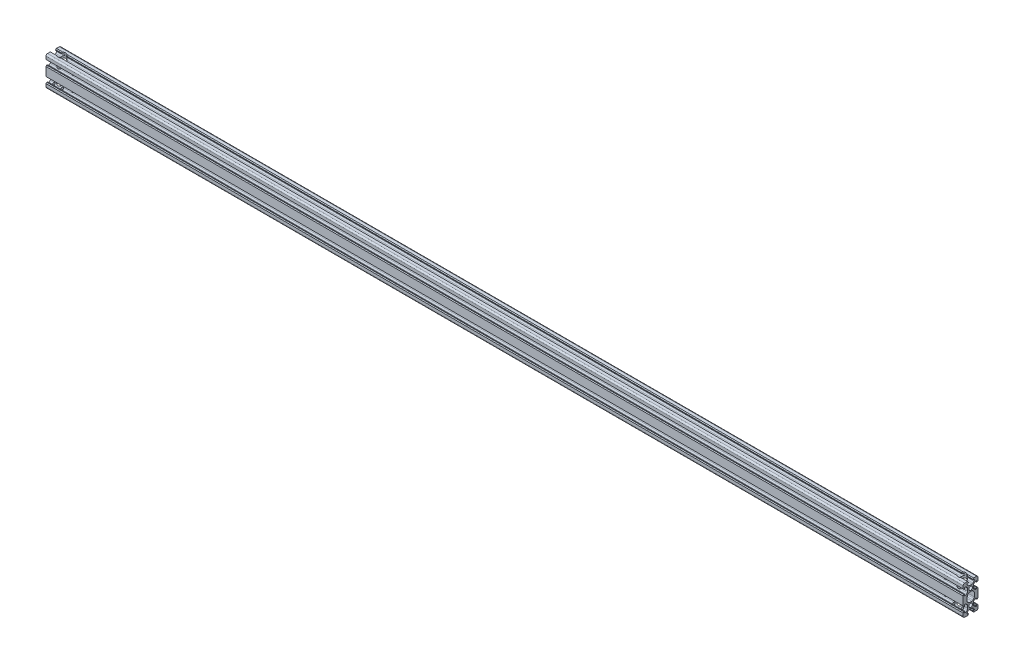
SolidWorks part; units mm, degrees
ref_plane "Front Plane" through (0, 0, 0) normal (0, 0, 1) x (1, 0, 0)
ref_plane "Top Plane" through (0, 0, 0) normal (0, 1, 0) x (1, 0, 0)
ref_plane "Right Plane" through (0, 0, 0) normal (1, 0, 0) x (0, 0, -1)
sketch "Sketch1" plane through (0, 0, 0) normal (1, 0, 0) x (0, 0, -1)
  line B0 (6.9, 38) -> (5, 38)
  line B1 (19, 6.9) -> (20, 5.9)
  line B2 (14.4142, 15.8284) -> (13.1236, 14.5379)
  line B3 (20, 14.1) -> (19, 13.1)
  line B4 (15.8284, 5.5858) -> (14.5379, 6.8764)
  line B5 (17.2426, 5) -> (18, 5)
  line B6 (18, 6.9) -> (18, 5)
  line B7 (17.2426, 15) -> (18, 15)
  line B8 (8.2906, 13.9521) -> (11.7094, 13.9521)
  line B9 (18, 15) -> (18, 13.1)
  line B10 (18, 13.1) -> (19, 13.1)
  line B11 (18, 6.9) -> (19, 6.9)
  line B12 (13.9521, 11.7094) -> (13.9521, 8.2906)
  line B13 (6.8764, 14.5379) -> (5.5858, 15.8284)
  line B14 (20, 5.9) -> (20, 2)
  line B15 (14.5379, 13.1236) -> (15.8284, 14.4142)
  line B16 (6.9, 1) -> (5.9, 0)
  line B17 (18, 0) -> (14.1, 0)
  line B18 (14.1, 0) -> (13.1, 1)
  line B19 (5.5858, 4.1716) -> (6.8764, 5.4621)
  line B20 (5, 2.7574) -> (5, 2)
  line B21 (6.9, 2) -> (5, 2)
  line B22 (15, 2.7574) -> (15, 2)
  line B23 (15, 2) -> (13.1, 2)
  line B24 (13.1, 2) -> (13.1, 1)
  line B25 (6.9, 2) -> (6.9, 1)
  line B26 (11.7094, 6.0479) -> (8.2906, 6.0479)
  line B27 (5.9, 0) -> (2, 0)
  line B28 (13.1236, 5.4621) -> (14.4142, 4.1716)
  line B29 (1, 13.1) -> (0, 14.1)
  line B30 (0, 2) -> (0, 5.9)
  line B31 (0, 5.9) -> (1, 6.9)
  line B32 (4.1716, 14.4142) -> (5.4621, 13.1236)
  line B33 (2.7574, 15) -> (2, 15)
  line B34 (2, 13.1) -> (2, 15)
  line B35 (2.7574, 5) -> (2, 5)
  line B36 (2, 5) -> (2, 6.9)
  line B37 (2, 6.9) -> (1, 6.9)
  line B38 (2, 13.1) -> (1, 13.1)
  line B39 (6.0479, 8.2906) -> (6.0479, 11.7094)
  line B40 (5.4621, 6.8764) -> (4.1716, 5.5858)
  line B41 (19, 26.9) -> (20, 25.9)
  line B42 (15, 38) -> (13.1, 38)
  line B43 (14.1, 40) -> (13.1, 39)
  line B44 (14.4142, 35.8284) -> (13.1236, 34.5379)
  line B45 (18, 35) -> (18, 33.1)
  line B46 (6.9, 38) -> (6.9, 39)
  line B47 (18, 40) -> (14.1, 40)
  line B48 (5.9, 40) -> (2, 40)
  line B49 (0, 25.9) -> (1, 26.9)
  line B50 (17.2426, 25) -> (18, 25)
  line B51 (5, 37.2426) -> (5, 38)
  line B52 (18, 26.9) -> (19, 26.9)
  line B53 (13.1, 38) -> (13.1, 39)
  line B54 (2, 26.9) -> (1, 26.9)
  line B55 (20, 34.1) -> (19, 33.1)
  line B56 (5, 22.7574) -> (5, 17.2426)
  line B57 (20, 34.1) -> (20, 38)
  line B58 (0, 38) -> (0, 34.1)
  line B59 (13.1236, 25.4621) -> (14.4142, 24.1716)
  line B60 (2, 25) -> (2, 26.9)
  line B61 (6.0479, 28.2906) -> (6.0479, 31.7094)
  line B62 (18, 33.1) -> (19, 33.1)
  line B63 (15, 37.2426) -> (15, 38)
  line B64 (2, 33.1) -> (2, 35)
  line B65 (18, 26.9) -> (18, 25)
  line B66 (11.7094, 26.0479) -> (8.2906, 26.0479)
  line B67 (17.2426, 35) -> (18, 35)
  line B68 (20, 25.9) -> (20, 14.1)
  line B69 (1, 33.1) -> (0, 34.1)
  line B70 (14.5379, 33.1236) -> (15.8284, 34.4142)
  line B71 (4.1716, 34.4142) -> (5.4621, 33.1236)
  line B72 (13.9521, 31.7094) -> (13.9521, 28.2906)
  line B73 (2.7574, 35) -> (2, 35)
  line B74 (8.2906, 33.9521) -> (11.7094, 33.9521)
  line B75 (6.9, 39) -> (5.9, 40)
  line B76 (5.4621, 26.8764) -> (4.1716, 25.5858)
  line B77 (0, 14.1) -> (0, 25.9)
  line B78 (5.5858, 24.1716) -> (6.8764, 25.4621)
  line B79 (15.8284, 25.5858) -> (14.5379, 26.8764)
  line B80 (6.8764, 34.5379) -> (5.5858, 35.8284)
  line B81 (15, 22.7574) -> (15, 17.2426)
  line B82 (2.7574, 25) -> (2, 25)
  line B83 (2, 33.1) -> (1, 33.1)
  circle B84 centre (10, 10) radius 2.5
  arc B85 (5.4621, 13.1236) -> (6.0479, 11.7094) centre (4.0479, 11.7094) cw
  arc B86 (4.1716, 14.4142) -> (2.7574, 15) centre (2.7574, 13) ccw
  arc B87 (5, 17.2426) -> (5.5858, 15.8284) centre (7, 17.2426) ccw
  arc B88 (15, 17.2426) -> (14.4142, 15.8284) centre (13, 17.2426) cw
  arc B89 (17.2426, 15) -> (15.8284, 14.4142) centre (17.2426, 13) ccw
  arc B90 (15.8284, 5.5858) -> (17.2426, 5) centre (17.2426, 7) ccw
  arc B91 (15, 2.7574) -> (14.4142, 4.1716) centre (13, 2.7574) ccw
  arc B92 (5.5858, 4.1716) -> (5, 2.7574) centre (7, 2.7574) ccw
  arc B93 (2.7574, 5) -> (4.1716, 5.5858) centre (2.7574, 7) ccw
  arc B94 (6.0479, 8.2906) -> (5.4621, 6.8764) centre (4.0479, 8.2906) cw
  arc B95 (6.8764, 5.4621) -> (8.2906, 6.0479) centre (8.2906, 4.0479) cw
  arc B96 (11.7094, 6.0479) -> (13.1236, 5.4621) centre (11.7094, 4.0479) cw
  arc B97 (14.5379, 6.8764) -> (13.9521, 8.2906) centre (15.9521, 8.2906) cw
  arc B98 (13.9521, 11.7094) -> (14.5379, 13.1236) centre (15.9521, 11.7094) cw
  arc B99 (11.7094, 13.9521) -> (13.1236, 14.5379) centre (11.7094, 15.9521) ccw
  arc B100 (8.2906, 13.9521) -> (6.8764, 14.5379) centre (8.2906, 15.9521) cw
  arc B101 (2, 0) -> (0, 2) centre (2, 2) cw
  arc B102 (20, 2) -> (18, 0) centre (18, 2) cw
  arc B103 (11.7094, 26.0479) -> (13.1236, 25.4621) centre (11.7094, 24.0479) cw
  arc B104 (13.9521, 31.7094) -> (14.5379, 33.1236) centre (15.9521, 31.7094) cw
  arc B105 (14.5379, 26.8764) -> (13.9521, 28.2906) centre (15.9521, 28.2906) cw
  arc B106 (5.5858, 24.1716) -> (5, 22.7574) centre (7, 22.7574) ccw
  arc B107 (5, 37.2426) -> (5.5858, 35.8284) centre (7, 37.2426) ccw
  arc B108 (11.7094, 33.9521) -> (13.1236, 34.5379) centre (11.7094, 35.9521) ccw
  arc B109 (15, 22.7574) -> (14.4142, 24.1716) centre (13, 22.7574) ccw
  arc B110 (2.7574, 25) -> (4.1716, 25.5858) centre (2.7574, 27) ccw
  arc B111 (15, 37.2426) -> (14.4142, 35.8284) centre (13, 37.2426) cw
  circle B112 centre (10, 30) radius 2.5
  arc B113 (8.2906, 33.9521) -> (6.8764, 34.5379) centre (8.2906, 35.9521) cw
  arc B114 (6.0479, 28.2906) -> (5.4621, 26.8764) centre (4.0479, 28.2906) cw
  arc B115 (6.8764, 25.4621) -> (8.2906, 26.0479) centre (8.2906, 24.0479) cw
  arc B116 (4.1716, 34.4142) -> (2.7574, 35) centre (2.7574, 33) ccw
  arc B117 (15.8284, 25.5858) -> (17.2426, 25) centre (17.2426, 27) ccw
  arc B118 (5.4621, 33.1236) -> (6.0479, 31.7094) centre (4.0479, 31.7094) cw
  arc B119 (2, 40) -> (0, 38) centre (2, 38) ccw
  arc B120 (17.2426, 35) -> (15.8284, 34.4142) centre (17.2426, 33) ccw
  arc B121 (20, 38) -> (18, 40) centre (18, 38) ccw
sketch_block_instance "2040-1"
sketch_block "2040" parameters "D1"=2, "D2"=2
extrude "Boss-Extrude1" add sketch "Sketch1" along normal blind 1240
sketch "Sketch2" plane through (0, 40, 0) normal (0, 1, 0) x (1, 0, 0)
  line L0 (11.5, 10) -> (0, 10) construction
  line L1 (1228.5, 10) -> (1240, 10) construction
  line L2 (620, 62.4179) -> (620, -29.0265) construction
  circle A0 centre (1228.5, 10) radius 5
  circle A1 centre (11.5, 10) radius 5
extrude "Cut-Extrude1" cut sketch "Sketch2" against normal through all
sketch "Sketch3" plane through (0, 0, -20) normal (0, 0, -1) x (-1, 0, 0)
  line L0 (-20, 40) -> (-1220, 40) construction
  line L1 (-1240, 40) -> (0, 40) construction
  line L2 (-1220, 20) -> (-1210, 20) construction
  line L3 (-1210, 34.1) -> (-1210, 25.9) construction
  line L4 (-1240, 34.1) -> (0, 34.1) construction
  line L5 (-1240, 25.9) -> (0, 25.9) construction
  line L6 (-1210, 14.1) -> (-1210, 5.9) construction
  line L7 (-1240, 14.1) -> (0, 14.1) construction
  line L8 (-1240, 5.9) -> (0, 5.9) construction
  line L9 (-620, 40) -> (-620, 111.1133) construction
  circle A0 centre (-1210, 30) radius 2.5
  circle A1 centre (-1210, 10) radius 2.5
  circle A2 centre (-30, 30) radius 2.5
  circle A3 centre (-30, 10) radius 2.5
  point P5 (-620, 40)
extrude "Cut-Extrude2" cut sketch "Sketch3" against normal through all
sketch "Sketch4" plane through (0, 0, -20) normal (0, 0, -1) x (-1, 0, 0)
  line L0 (-620, 40) -> (-620, 127.7349) construction
  circle A0 centre (-1210, 30) radius 5
  circle A1 centre (-1210, 10) radius 5
  circle A2 centre (-30, 10) radius 5
  circle A3 centre (-30, 30) radius 5
extrude "Cut-Extrude3" cut sketch "Sketch4" against normal up to surface (6.0479 mm away) up to face at (1218.7996, 30, -13.9521)
sketch "Sketch5" plane through (0, 0, 0) normal (0, -1, 0) x (1, 0, 0)
  line L0 (0, -10) -> (26, -10) construction
  line L2 (26, -10) -> (36, -10) construction
  line L3 (11.5, -10) -> (5.8431, -4.3431) construction
  line L4 (620, 0) -> (620, -35.0806) construction
  line L6 (1228.5, -10) -> (1234.1569, -4.3431) construction
  line L7 (1214, -10) -> (1204, -10) construction
  line L8 (1240, -10) -> (1214, -10) construction
  circle A0 centre (26, -10) radius 1.4
  circle A1 centre (36, -10) radius 1.4
  circle A2 centre (11.5, -10) radius 8 construction
  circle A3 centre (5.8431, -4.3431) radius 1.4
  circle A4 centre (17.1569, -4.3431) radius 1.4
  circle A5 centre (17.1569, -15.6569) radius 1.4
  circle A6 centre (5.8431, -15.6569) radius 1.4
  circle A7 centre (1228.5, -10) radius 8 construction
  circle A8 centre (1234.1569, -15.6569) radius 1.4
  circle A9 centre (1222.8431, -15.6569) radius 1.4
  circle A10 centre (1222.8431, -4.3431) radius 1.4
  circle A11 centre (1234.1569, -4.3431) radius 1.4
  circle A12 centre (1204, -10) radius 1.4
  circle A13 centre (1214, -10) radius 1.4
  point P24 (11.5, -10)
extrude "Cut-Extrude4" cut sketch "Sketch5" against normal blind 10
